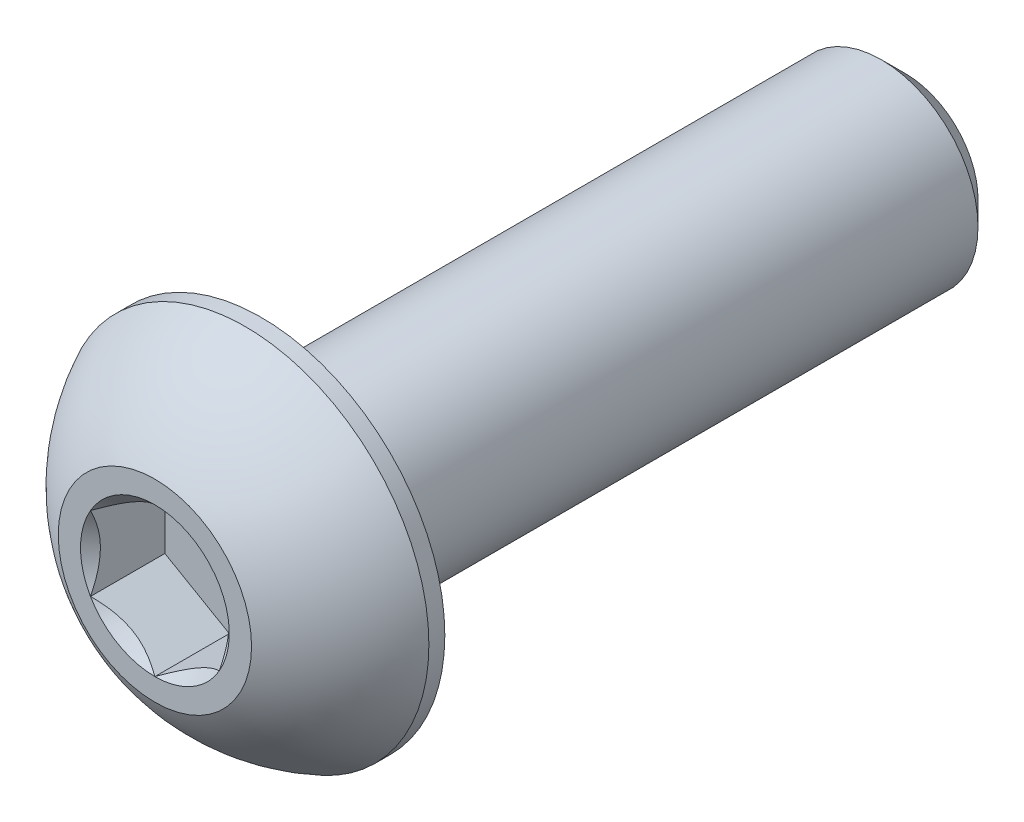
SolidWorks part; units mm, degrees
ref_plane "Front" through (0, 0, 0) normal (0, 0, 1) x (1, 0, 0)
ref_plane "Top" through (0, 0, 0) normal (0, 1, 0) x (1, 0, 0)
ref_plane "Right" through (0, 0, 0) normal (1, 0, 0) x (0, 0, -1)
sketch "Sketch1" plane through (0, 0, 0) normal (1, 0, 0) x (0, 0, -1)
  line L2 (1.65, 1.5) -> (11.65, 1.5)
  line L3 (11.65, 1.5) -> (11.65, 0)
  line L4 (11.65, 0) -> (1.65, 0)
  line L6 (1.4025, 2.85) -> (1.65, 2.85) construction
  line L7 (11.65, 1.5) -> (11.65, -1.5) construction
  line L8 (0, 0) -> (1.65, 0) construction
  line L9 (1.65, 2.85) -> (1.65, -2.85) construction
  line L11 (1.65, 1.5) -> (1.65, 0)
  line L13 (0, 1) -> (0, -1) construction
  line L14 (0, 1) -> (0, 1.5) construction
  arc A3 (0, 1.5) -> (1.4025, 2.85) centre (2.7948, 0) cw construction
  dimension "D1" = 0.2475
revolve "Revolve1" add sketch "Sketch1" angle 360 mid plane about L4
sketch "Sketch3" plane through (0, 0, -11.65) normal (0, 0, -1) x (-1, 0, 0)
  circle A0 centre (0, 0) radius 1.5
curve "Helix/Spiral1" pitch 0.5 height 10.5 turns 21
sketch "Sketch2" plane through (0, 0, 0) normal (1, 0, 0) x (0, 0, -1)
  line L0 (11.65, 1.5) -> (12.0875, 1.5)
  line L1 (12.0875, 1.5) -> (11.9, 1.1752)
  line L2 (11.9, 1.1752) -> (11.8375, 1.1752)
  line L3 (11.8375, 1.1752) -> (11.65, 1.5)
  line L4 (11.7438, 1.3376) -> (11.9938, 1.3376) construction
  dimension "D1" = 60
  dimension "D2" = 0.0625
  dimension "D3" = 0.25
chamfer "Chamfer1" distance 0.375 angle 45 1 edges at (0, 1.5, -11.65)
sweep "Cut-Sweep1" [suppressed] cut profiles "Sketch2" path "Helix/Spiral1"
sketch "Sketch7" plane through (0, 0, 0) normal (1, 0, 0) x (0, 0, -1)
  line L6 (1.4025, 2.85) -> (1.65, 2.85) construction
  line L8 (0, 0) -> (1.65, 0) construction
  line L11 (1.65, 2.85) -> (1.65, -2.85) construction
  line L12 (1.4025, 2.85) -> (1.65, 2.85)
  line L13 (0, 0) -> (1.65, 0)
  line L14 (0, 1) -> (0, -1) construction
  line L15 (1.65, 2.85) -> (1.65, 0)
  line L16 (0, 1.5) -> (0, 0)
  arc A2 (1.4025, 2.85) -> (0, 1.5) centre (2.7948, 0) ccw construction
  arc A3 (1.4025, 2.85) -> (0, 1.5) centre (2.7948, 0) ccw
revolve "Revolve2" add sketch "Sketch7" angle 360 mid plane about L13
sketch "Sketch5" plane through (0, 0, 0) normal (0, 0, 1) x (1, 0, 0)
  line L1 (1, -0.5774) -> (1, 0.5774)
  line L2 (1, 0.5774) -> (0, 1.1547)
  line L3 (0, 1.1547) -> (-1, 0.5774)
  line L4 (-1, 0.5774) -> (-1, -0.5774)
  line L5 (-1, -0.5774) -> (0, -1.1547)
  line L6 (0, -1.1547) -> (1, -0.5774)
  circle A0 centre (0, 0) radius 1 construction
extrude "Cut-Extrude2" cut sketch "Sketch5" against normal blind 1.155
sketch "Sketch6" plane through (0, 0, 0) normal (0, 0, 1) x (1, 0, 0)
  circle A0 centre (0, 0) radius 1.1547
extrude "Cut-Extrude3" cut sketch "Sketch6" against normal blind 1.155 draft 45
sketch "Sketch9" [suppressed] plane through (0, 0, -4.2164) normal (0, 0, 1) x (1, 0, 0)
  circle A2 centre (0, 0) radius 3.9687
extrude "Boss-Extrude2" [suppressed] add sketch "Sketch9" against normal offset from surface (9.525 mm away) 28.575
sketch "Sketch10" plane through (0, 0, 0) normal (1, 0, 0) x (0, 0, -1)
  line L0 (11.65, 1.5) -> (11.65, -1.5) construction
  point P0 (10.9, -1.5)
  dimension "D1" = 0.75
equation "\"D3@Helix/Spiral1\" = \"Lg@Sketch1\" + \"D4@Helix/Spiral1\""
equation "\"D2@Sketch2\" = \"D4@Helix/Spiral1\" * .125"
equation "\"D3@Sketch2\" = \"D4@Helix/Spiral1\" * .5"
equation "\"D1@Chamfer1\" = \"D4@Helix/Spiral1\" * .75"
equation "\"D1@Cut-Extrude2\" = \"Head Ht@Sketch1\" * .7"
equation "\"D1@Sketch1\" = \"Head Ht@Sketch1\" * .15"
equation "\"D1@Sketch10\" = \"D4@Helix/Spiral1\" * 1.5"
equation "\"D1@Cut-Extrude3\" = \"D1@Cut-Extrude2\""
